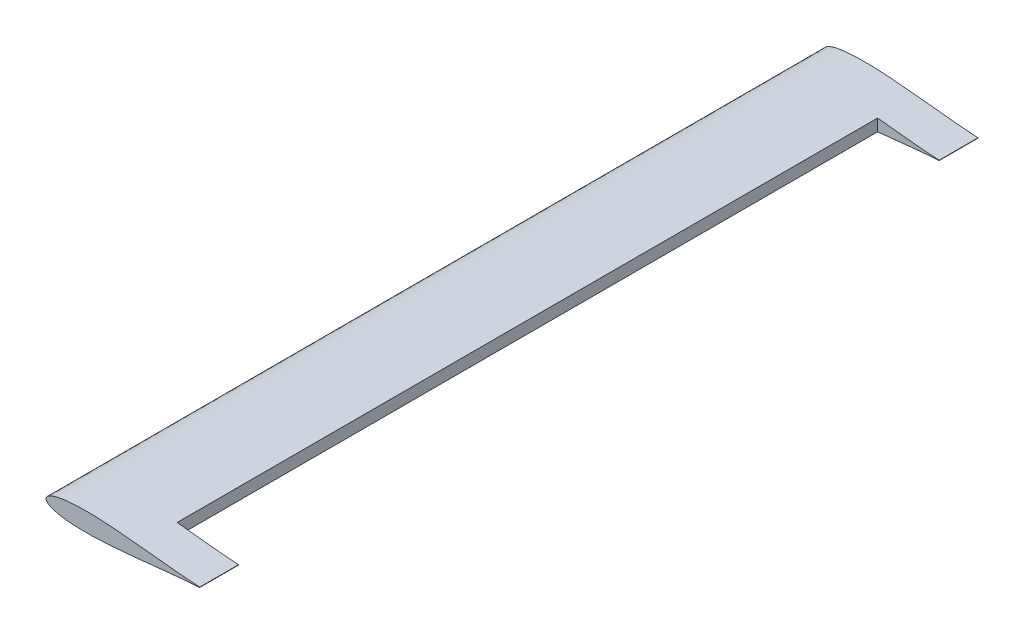
SolidWorks part; units mm, degrees
other "Markup1"
sketch "Sketch3" plane through (-0.0553, -7.355, 609.6) normal (0, 0, 1) x (1, 0, 0)
ref_plane "Front Plane" through (0, 0, 0) normal (0, 0, 1) x (1, 0, 0)
ref_plane "Top Plane" through (0, 0, 0) normal (0, 1, 0) x (1, 0, 0)
ref_plane "Right Plane" through (0, 0, 0) normal (1, 0, 0) x (0, 0, -1)
curve "Curve1"
  spline degree 3 poles (25.3337, -0.0003, 0) (25.4166, 0, 0) (25.3337, 0.0003, 0) (25.2654, 0.0018, 0) (25.098, 0.0055, 0) (24.8899, 0.0127, 0) (24.614, 0.0243, 0) (24.2833, 0.0411, 0) (23.8951, 0.064, 0) (23.4526, 0.0935, 0) (22.9577, 0.1302, 0) (22.4128, 0.1742, 0) (21.8206, 0.2257, 0) (21.184, 0.2845, 0) (20.5061, 0.3502, 0) (19.7901, 0.4224, 0) (19.0396, 0.5004, 0) (18.2582, 0.5832, 0) (17.4498, 0.6697, 0) (16.6182, 0.7589, 0) (15.7675, 0.8494, 0) (14.9019, 0.9396, 0) (14.0255, 1.0282, 0) (13.1427, 1.1135, 0) (12.2578, 1.1941, 0) (11.3749, 1.2683, 0) (10.4986, 1.3345, 0) (9.6329, 1.3915, 0) (8.7821, 1.4377, 0) (7.9504, 1.4721, 0) (7.1418, 1.4935, 0) (6.3603, 1.501, 0) (5.6096, 1.4941, 0) (4.8934, 1.4721, 0) (4.2152, 1.4349, 0) (3.5783, 1.3824, 0) (2.9857, 1.3149, 0) (2.4403, 1.233, 0) (1.9447, 1.1371, 0) (1.5013, 1.0283, 0) (1.1121, 0.9078, 0) (0.7787, 0.7769, 0) (0.5025, 0.6369, 0) (0.2843, 0.4891, 0) (0.1244, 0.334, 0) (0.024, 0.1711, 0) (-0.0113, 0, 0) (0.024, -0.1711, 0) (0.1244, -0.334, 0) (0.2843, -0.4891, 0) (0.5025, -0.6369, 0) (0.7787, -0.7769, 0) (1.1121, -0.9078, 0) (1.5013, -1.0283, 0) (1.9447, -1.1371, 0) (2.4403, -1.233, 0) (2.9857, -1.3149, 0) (3.5783, -1.3824, 0) (4.2152, -1.4349, 0) (4.8934, -1.4721, 0) (5.6096, -1.4941, 0) (6.3603, -1.501, 0) (7.1418, -1.4935, 0) (7.9504, -1.4721, 0) (8.7821, -1.4377, 0) (9.6329, -1.3915, 0) (10.4986, -1.3345, 0) (11.3749, -1.2683, 0) (12.2578, -1.1941, 0) (13.1427, -1.1135, 0) (14.0255, -1.0282, 0) (14.9019, -0.9396, 0) (15.7675, -0.8494, 0) (16.6182, -0.7589, 0) (17.4498, -0.6697, 0) (18.2582, -0.5832, 0) (19.0396, -0.5004, 0) (19.7901, -0.4224, 0) (20.5061, -0.3502, 0) (21.184, -0.2845, 0) (21.8206, -0.2257, 0) (22.4128, -0.1742, 0) (22.9577, -0.1302, 0) (23.4526, -0.0935, 0) (23.8951, -0.064, 0) (24.2833, -0.0411, 0) (24.614, -0.0243, 0) (24.8899, -0.0127, 0) (25.098, -0.0055, 0) (25.2654, -0.0018, 0) (25.3337, -0.0003, 0) (25.4166, 0, 0) (25.3337, 0.0003, 0) knots -0.005355 -0.002385 -0.000597 0 0.000597 0.002385 0.005355 0.009495 0.014784 0.021198 0.028708 0.037278 0.046868 0.05743 0.068917 0.081271 0.094432 0.108338 0.122919 0.138103 0.153815 0.169978 0.186509 0.203327 0.220349 0.237488 0.25466 0.271779 0.288763 0.305527 0.32199 0.338073 0.353702 0.368803 0.383306 0.397149 0.410269 0.422614 0.434133 0.444783 0.454527 0.463337 0.471194 0.478092 0.484042 0.489082 0.493295 0.496842 0.5 0.503158 0.506705 0.510918 0.515958 0.521908 0.528806 0.536663 0.545473 0.555218 0.565867 0.577386 0.589731 0.602851 0.616694 0.631197 0.646298 0.661927 0.67801 0.694473 0.711237 0.728221 0.74534 0.762512 0.779651 0.796673 0.813491 0.830023 0.846185 0.861897 0.877081 0.891662 0.905568 0.918729 0.931083 0.94257 0.953133 0.962722 0.971292 0.978802 0.985216 0.990505 0.994645 0.997615 0.999403 1 1.000597 1.002385 1.005355 periodic
sketch "Sketch2" plane through (0, 0, 0) normal (0, 0, 1) x (1, 0, 0)
  line L0 (0, 0) -> (25.4, 0) construction
  line L1 (0, 0) -> (124.46, 0) construction
  line L2 (120.381, 0.1319) -> (120.381, -0.1319)
  line L3 (62.23, 0) -> (62.23, 5.6527) construction
  spline S0 degree 3 poles (25.3337, -0.0003) (25.4166, 0) (25.3337, 0.0003) (25.2654, 0.0018) (25.098, 0.0055) (24.8899, 0.0127) (24.614, 0.0243) (24.2833, 0.0411) (23.8951, 0.064) (23.4526, 0.0935) (22.9577, 0.1302) (22.4128, 0.1742) (21.8206, 0.2257) (21.184, 0.2845) (20.5061, 0.3502) (19.7901, 0.4224) (19.0396, 0.5004) (18.2582, 0.5832) (17.4498, 0.6697) (16.6182, 0.7589) (15.7675, 0.8494) (14.9019, 0.9396) (14.0255, 1.0282) (13.1427, 1.1135) (12.2578, 1.1941) (11.3749, 1.2683) (10.4986, 1.3345) (9.6329, 1.3915) (8.7821, 1.4377) (7.9504, 1.4721) (7.1418, 1.4935) (6.3603, 1.501) (5.6096, 1.4941) (4.8934, 1.4721) (4.2152, 1.4349) (3.5783, 1.3824) (2.9857, 1.3149) (2.4403, 1.233) (1.9447, 1.1371) (1.5013, 1.0283) (1.1121, 0.9078) (0.7787, 0.7769) (0.5025, 0.6369) (0.2843, 0.4891) (0.1244, 0.334) (0.024, 0.1711) (-0.0113, 0) (0.024, -0.1711) (0.1244, -0.334) (0.2843, -0.4891) (0.5025, -0.6369) (0.7787, -0.7769) (1.1121, -0.9078) (1.5013, -1.0283) (1.9447, -1.1371) (2.4403, -1.233) (2.9857, -1.3149) (3.5783, -1.3824) (4.2152, -1.4349) (4.8934, -1.4721) (5.6096, -1.4941) (6.3603, -1.501) (7.1418, -1.4935) (7.9504, -1.4721) (8.7821, -1.4377) (9.6329, -1.3915) (10.4986, -1.3345) (11.3749, -1.2683) (12.2578, -1.1941) (13.1427, -1.1135) (14.0255, -1.0282) (14.9019, -0.9396) (15.7675, -0.8494) (16.6182, -0.7589) (17.4498, -0.6697) (18.2582, -0.5832) (19.0396, -0.5004) (19.7901, -0.4224) (20.5061, -0.3502) (21.184, -0.2845) (21.8206, -0.2257) (22.4128, -0.1742) (22.9577, -0.1302) (23.4526, -0.0935) (23.8951, -0.064) (24.2833, -0.0411) (24.614, -0.0243) (24.8899, -0.0127) (25.098, -0.0055) (25.2654, -0.0018) (25.3337, -0.0003) (25.4166, 0) (25.3337, 0.0003) knots -0.005355 -0.002385 -0.000597 0 0.000597 0.002385 0.005355 0.009495 0.014784 0.021198 0.028708 0.037278 0.046868 0.05743 0.068917 0.081271 0.094432 0.108338 0.122919 0.138103 0.153815 0.169978 0.186509 0.203327 0.220349 0.237488 0.25466 0.271779 0.288763 0.305527 0.32199 0.338073 0.353702 0.368803 0.383306 0.397149 0.410269 0.422614 0.434133 0.444783 0.454527 0.463337 0.471194 0.478092 0.484042 0.489082 0.493295 0.496842 0.5 0.503158 0.506705 0.510918 0.515958 0.521908 0.528806 0.536663 0.545473 0.555218 0.565867 0.577386 0.589731 0.602851 0.616694 0.631197 0.646298 0.661927 0.67801 0.694473 0.711237 0.728221 0.74534 0.762512 0.779651 0.796673 0.813491 0.830023 0.846185 0.861897 0.877081 0.891662 0.905568 0.918729 0.931083 0.94257 0.953133 0.962722 0.971292 0.978802 0.985216 0.990505 0.994645 0.997615 0.999403 1 1.000597 1.002385 1.005355 only from (25.4, 0) to (25.4, 0) construction
  spline S1 degree 3 poles (25.3337, -0.0003) (25.4166, 0) (25.3337, 0.0003) (25.2654, 0.0018) (25.098, 0.0055) (24.8899, 0.0127) (24.614, 0.0243) (24.2833, 0.0411) (23.8951, 0.064) (23.4526, 0.0935) (22.9577, 0.1302) (22.4128, 0.1742) (21.8206, 0.2257) (21.184, 0.2845) (20.5061, 0.3502) (19.7901, 0.4224) (19.0396, 0.5004) (18.2582, 0.5832) (17.4498, 0.6697) (16.6182, 0.7589) (15.7675, 0.8494) (14.9019, 0.9396) (14.0255, 1.0282) (13.1427, 1.1135) (12.2578, 1.1941) (11.3749, 1.2683) (10.4986, 1.3345) (9.6329, 1.3915) (8.7821, 1.4377) (7.9504, 1.4721) (7.1418, 1.4935) (6.3603, 1.501) (5.6096, 1.4941) (4.8934, 1.4721) (4.2152, 1.4349) (3.5783, 1.3824) (2.9857, 1.3149) (2.4403, 1.233) (1.9447, 1.1371) (1.5013, 1.0283) (1.1121, 0.9078) (0.7787, 0.7769) (0.5025, 0.6369) (0.2843, 0.4891) (0.1244, 0.334) (0.024, 0.1711) (-0.0113, 0) (0.024, -0.1711) (0.1244, -0.334) (0.2843, -0.4891) (0.5025, -0.6369) (0.7787, -0.7769) (1.1121, -0.9078) (1.5013, -1.0283) (1.9447, -1.1371) (2.4403, -1.233) (2.9857, -1.3149) (3.5783, -1.3824) (4.2152, -1.4349) (4.8934, -1.4721) (5.6096, -1.4941) (6.3603, -1.501) (7.1418, -1.4935) (7.9504, -1.4721) (8.7821, -1.4377) (9.6329, -1.3915) (10.4986, -1.3345) (11.3749, -1.2683) (12.2578, -1.1941) (13.1427, -1.1135) (14.0255, -1.0282) (14.9019, -0.9396) (15.7675, -0.8494) (16.6182, -0.7589) (17.4498, -0.6697) (18.2582, -0.5832) (19.0396, -0.5004) (19.7901, -0.4224) (20.5061, -0.3502) (21.184, -0.2845) (21.8206, -0.2257) (22.4128, -0.1742) (22.9577, -0.1302) (23.4526, -0.0935) (23.8951, -0.064) (24.2833, -0.0411) (24.614, -0.0243) (24.8899, -0.0127) (25.098, -0.0055) (25.2654, -0.0018) (25.3337, -0.0003) (25.4166, 0) (25.3337, 0.0003) knots -0.005355 -0.002385 -0.000597 0 0.000597 0.002385 0.005355 0.009495 0.014784 0.021198 0.028708 0.037278 0.046868 0.05743 0.068917 0.081271 0.094432 0.108338 0.122919 0.138103 0.153815 0.169978 0.186509 0.203327 0.220349 0.237488 0.25466 0.271779 0.288763 0.305527 0.32199 0.338073 0.353702 0.368803 0.383306 0.397149 0.410269 0.422614 0.434133 0.444783 0.454527 0.463337 0.471194 0.478092 0.484042 0.489082 0.493295 0.496842 0.5 0.503158 0.506705 0.510918 0.515958 0.521908 0.528806 0.536663 0.545473 0.555218 0.565867 0.577386 0.589731 0.602851 0.616694 0.631197 0.646298 0.661927 0.67801 0.694473 0.711237 0.728221 0.74534 0.762512 0.779651 0.796673 0.813491 0.830023 0.846185 0.861897 0.877081 0.891662 0.905568 0.918729 0.931083 0.94257 0.953133 0.962722 0.971292 0.978802 0.985216 0.990505 0.994645 0.997615 0.999403 1 1.000597 1.002385 1.005355 only from (25.4, 0) to (25.4, 0) construction
  spline S2 degree 3 poles (120.381, 0.1319) (119.9463, 0.1527) (118.8798, 0.2078) (117.0858, 0.3137) (114.9178, 0.4584) (112.4927, 0.6382) (109.8228, 0.8537) (106.9211, 1.106) (103.8017, 1.394) (100.4797, 1.7159) (96.9715, 2.0698) (93.294, 2.4518) (89.4653, 2.8575) (85.5038, 3.2818) (81.4291, 3.7187) (77.2608, 4.162) (73.0193, 4.6041) (68.7252, 5.0383) (64.3994, 5.4564) (60.0631, 5.8512) (55.7372, 6.2145) (51.4429, 6.5392) (47.2011, 6.8181) (43.0324, 7.0448) (38.9571, 7.2131) (34.9951, 7.3181) (31.1655, 7.355) (27.4872, 7.3209) (23.9779, 7.2133) (20.6546, 7.0309) (17.5336, 6.7739) (14.6298, 6.4432) (11.9574, 6.0415) (9.5291, 5.5718) (7.3563, 5.0389) (5.4492, 4.4484) (3.8158, 3.8067) (2.4624, 3.1207) (1.3928, 2.3964) (0.6096, 1.6368) (0.1174, 0.8384) (-0.0553, 0) (0.1174, -0.8384) (0.6096, -1.6368) (1.3928, -2.3964) (2.4624, -3.1207) (3.8158, -3.8067) (5.4492, -4.4484) (7.3563, -5.0389) (9.5291, -5.5718) (11.9574, -6.0415) (14.6299, -6.4433) (17.5336, -6.7739) (20.6546, -7.0309) (23.9779, -7.2133) (27.4872, -7.3209) (31.1655, -7.355) (34.9951, -7.3181) (38.9571, -7.2131) (43.0324, -7.0448) (47.2011, -6.8181) (51.4429, -6.5392) (55.7372, -6.2145) (60.0631, -5.8512) (64.3994, -5.4564) (68.7252, -5.0383) (73.0193, -4.6041) (77.2608, -4.162) (81.4291, -3.7187) (85.5039, -3.2817) (89.4653, -2.8575) (93.294, -2.4518) (96.9715, -2.0698) (100.4797, -1.7159) (103.8017, -1.394) (106.9211, -1.106) (109.8228, -0.8537) (112.4927, -0.6382) (114.9179, -0.4584) (117.0858, -0.3137) (118.8798, -0.2078) (119.9463, -0.1527) (120.381, -0.1319) knots 0.016066 0.016066 0.016066 0.016066 0.021198 0.028708 0.037278 0.046868 0.05743 0.068917 0.081271 0.094432 0.108338 0.122919 0.138103 0.153815 0.169978 0.186509 0.203327 0.220349 0.237488 0.25466 0.271779 0.288763 0.305527 0.32199 0.338073 0.353702 0.368803 0.383306 0.397149 0.410269 0.422614 0.434133 0.444783 0.454527 0.463337 0.471194 0.478092 0.484042 0.489082 0.493295 0.496842 0.5 0.503158 0.506705 0.510918 0.515958 0.521908 0.528806 0.536663 0.545473 0.555218 0.565867 0.577386 0.589731 0.602851 0.616694 0.631197 0.646298 0.661927 0.67801 0.694473 0.711237 0.728221 0.74534 0.762512 0.779651 0.796673 0.813491 0.830023 0.846185 0.861897 0.877081 0.891662 0.905568 0.918729 0.931083 0.94257 0.953133 0.962722 0.971292 0.978802 0.983934 0.983934 0.983934 0.983934
  point P8 (0, 0)
  dimension "D1" = 124.46
  dimension "D2" = 4.079
  dimension "D3" = 5.6527
extrude "Boss-Extrude4" add sketch "Sketch2" along normal blind 609.6
sketch "Sketch4" plane through (0, 0, 0) normal (0, 1, 0) x (1, 0, 0)
  line L0 (0, 0) -> (0, -609.6) construction
  line L1 (0, -304.8) -> (120.381, -304.8) construction
  line L2 (120.381, -609.6) -> (120.381, 0) construction
  line L3 (120.381, -304.8) -> (72.2327, -304.8)
  line L4 (72.2327, -579.12) -> (72.2327, -30.48)
  line L5 (72.2327, -30.48) -> (171.5692, -30.48)
  line L6 (171.5692, -30.48) -> (171.5692, -579.12)
  line L7 (171.5692, -579.12) -> (72.2327, -579.12)
  point P12 (72.2327, -304.8)
  dimension "D1" = 48.1482
  dimension "D2" = 548.64
extrude "Cut-Extrude1" cut sketch "Sketch4" against normal through all both and the other way through all contours L7 L6 L5 L4 region at (121.901, 0, 304.8)
sketch "Sketch5" plane through (0, 0, 30.48) normal (0, 0, 1) x (1, 0, 0)
  line L0 (72.2327, 4.6824) -> (72.2327, -4.6824)
  line L1 (72.2327, 0) -> (120.381, 0) construction
  line L2 (120.381, -0.1319) -> (120.381, 0.1319) construction
  circle A0 centre (76.3067, 0) radius 4.0739 construction
  point P10 (76.3067, 0)
  dimension "D1" = 8.1479
